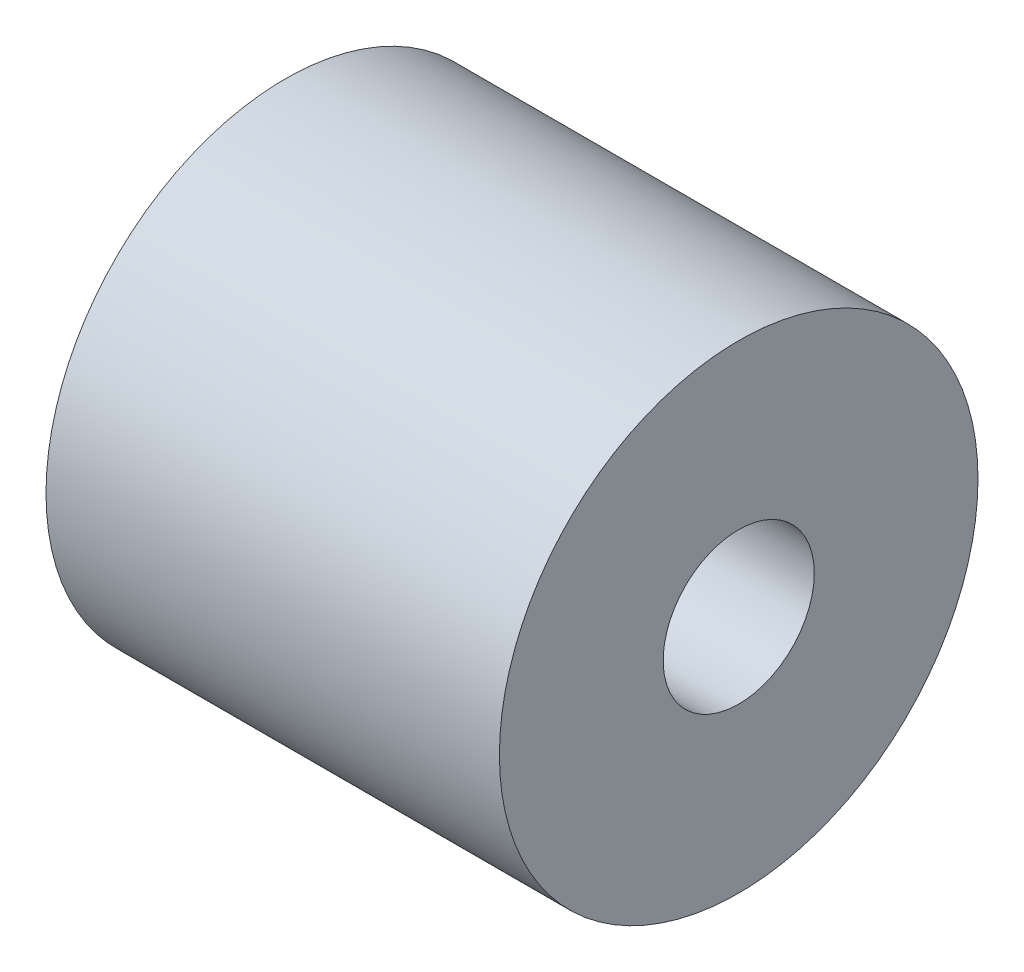
SolidWorks part; units mm, degrees
ref_plane "Front Plane" through (0, 0, 0) normal (0, 0, 1) x (1, 0, 0)
ref_plane "Top Plane" through (0, 0, 0) normal (0, 1, 0) x (1, 0, 0)
ref_plane "Right Plane" through (0, 0, 0) normal (1, 0, 0) x (0, 0, -1)
sketch "Sketch1" plane through (0, 0, 0) normal (1, 0, 0) x (0, 0, -1)
  circle A0 centre (0, 0) radius 9.5
  circle A1 centre (0, 0) radius 3
  dimension "D1" = 19
extrude "Boss-Extrude1" add sketch "Sketch1" along normal blind 9 and the other way blind 9
